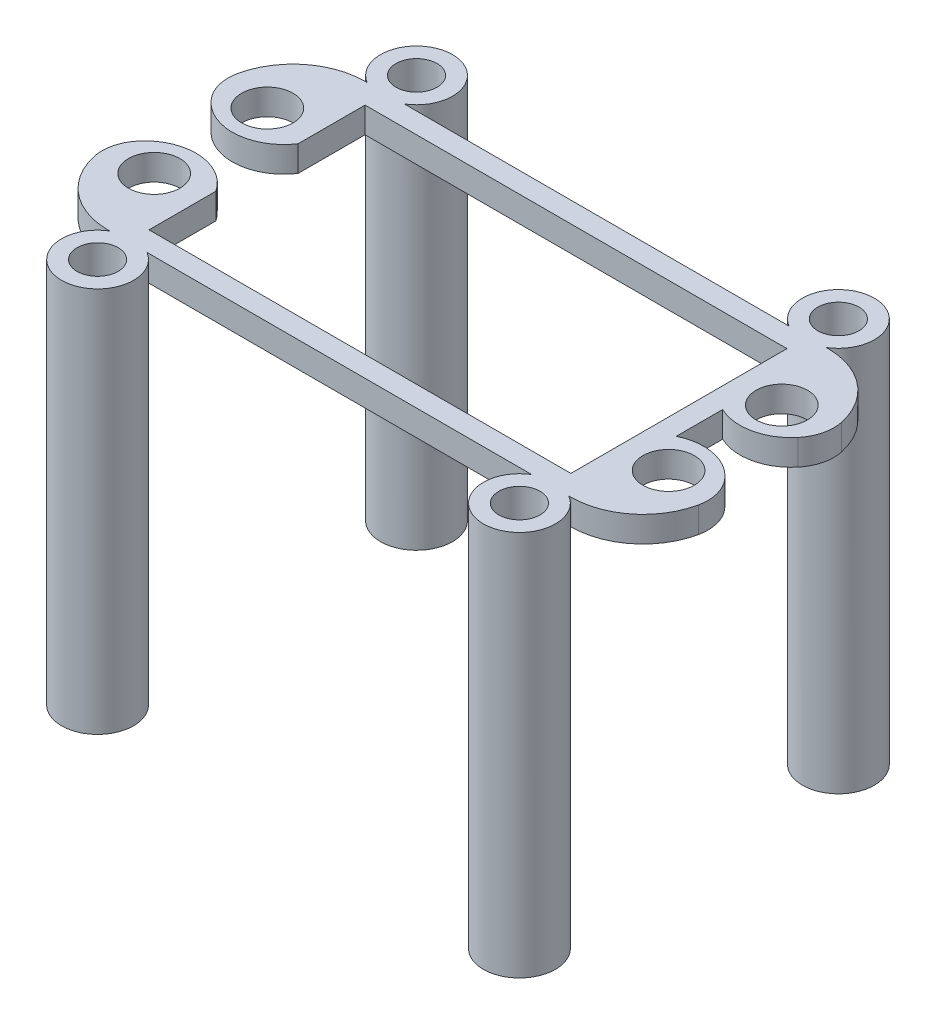
SolidWorks part; units mm, degrees
ref_plane "Front Plane" through (0, 0, 0) normal (0, 0, 1) x (1, 0, 0)
ref_plane "Top Plane" through (0, 0, 0) normal (0, 1, 0) x (1, 0, 0)
ref_plane "Right Plane" through (0, 0, 0) normal (1, 0, 0) x (0, 0, -1)
sketch "Sketch1" plane through (0, 0, 0) normal (0, 1, 0) x (1, 0, 0)
  line L0 (-20, 0) -> (-22, 0) construction
  line L1 (20.5, 10.5) -> (-20.5, 10.5)
  line L2 (20.5, 10.5) -> (20.5, -10.5)
  line L3 (20.5, -10.5) -> (-20.5, -10.5)
  line L4 (-20.5, 10.5) -> (-20.5, 4)
  line L5 (20.5, 10.5) -> (-20.5, -10.5) construction
  line L6 (20.5, -10.5) -> (-20.5, 10.5) construction
  line L7 (22.5, 12.5) -> (-22.5, 12.5)
  line L8 (22.5, 2.2557) -> (22.5, -2.2557)
  line L9 (22.5, -12.5) -> (-22.5, -12.5)
  line L11 (22.5, 12.5) -> (-22.5, -12.5) construction
  line L12 (22.5, -12.5) -> (-22.5, 12.5) construction
  line L16 (-20.5, -4) -> (-20.5, -10.5)
  line L17 (0, 0) -> (-37.8746, 0) construction
  line L18 (0, 0) -> (0, 8.5057) construction
  circle A0 centre (-25, 5.5) radius 2.5
  circle A1 centre (-25, -5.5) radius 2.5
  arc A4 (-22.5, 12.5) -> (-29.3504, 6.9605) centre (-22.5, 5.4945) ccw
  arc A5 (-20.5, 4) -> (-28.5206, 3.5732) centre (-24.6686, 6.761) cw
  arc A6 (-20.5, -4) -> (-28.5206, -3.5732) centre (-24.6686, -6.761) ccw
  arc A7 (-22.5, -12.5) -> (-29.3504, -6.9605) centre (-22.5, -5.4945) cw
  arc A8 (22.5, -12.5) -> (29.3504, -6.9605) centre (22.5, -5.4945) ccw
  circle A9 centre (25, -5.5) radius 2.5
  arc A10 (22.5, -2.2557) -> (28.5206, -3.5732) centre (24.6686, -6.761) cw
  circle A11 centre (25, 5.5) radius 2.5
  arc A12 (22.5, 2.2557) -> (28.5206, 3.5732) centre (24.6686, 6.761) ccw
  arc A13 (22.5, 12.5) -> (29.3504, 6.9605) centre (22.5, 5.4945) cw
  arc A14 (29.3504, -6.9605) -> (28.5206, -3.5732) centre (25.439, -6.1234) ccw
  arc A15 (28.5206, 3.5732) -> (29.3504, 6.9605) centre (25.439, 6.1234) ccw
  arc A16 (-28.5206, -3.5732) -> (-29.3504, -6.9605) centre (-25.439, -6.1234) ccw
  arc A17 (-29.3504, 6.9605) -> (-28.5206, 3.5732) centre (-25.439, 6.1234) ccw
  point P0 (0, 0)
  point P6 (0, 0)
  point P13 (-21, 0)
  point P36 (29.5055, -5.4945)
  point P46 (29.5055, 5.4945)
  point P49 (-29.5055, -5.4945)
  point P52 (-29.5055, 5.4945)
  dimension "D6" = 5
  dimension "D8" = 4.5
  dimension "D9" = 11
  dimension "D10" = 5
  dimension "D5" = 4
  dimension "D2" = 2
  dimension "D3" = 41
  dimension "D4" = 21
extrude "Boss-Extrude1" add sketch "Sketch1" along normal blind 2.5
sketch "Sketch4" plane through (0, 0, 0) normal (0, 1, 0) x (1, 0, 0)
  line L0 (-20.5, -10.5) -> (-20.5, -12.5) construction
  line L1 (-20.5, 10.5) -> (-20.5, 12.5) construction
  line L2 (22.5, 12.5) -> (-22.5, 12.5) construction
  line L3 (-20.5, 12.5) -> (-20.5, 15.5) construction
  line L4 (0, 0) -> (-12.5316, 0) construction
  line L5 (-22.5, -12.5) -> (22.5, -12.5) construction
  line L6 (-20.5, -12.5) -> (-20.5, -15.5) construction
  circle A0 centre (-20.5, 15.5) radius 2
  circle A1 centre (-20.5, 15.5) radius 3.5
  circle A2 centre (20.5, 15.5) radius 2
  circle A3 centre (20.5, 15.5) radius 3.5
  circle A4 centre (-20.5, -15.5) radius 2
  circle A5 centre (-20.5, -15.5) radius 3.5
  circle A6 centre (20.5, -15.5) radius 2
  circle A7 centre (20.5, -15.5) radius 3.5
  dimension "D1" = 1.5
  dimension "D2" = 4
  dimension "D3" = 1.5
  dimension "D4" = 4
  dimension "D8" = 4
  dimension "D9" = 1.5
  dimension "D10" = 1.5
  dimension "D11" = 4
  dimension "D5" = 41
  dimension "D6" = 3
  dimension "D7" = 41
  dimension "D12" = 3
extrude "Boss-Extrude2" add sketch "Sketch4" along normal up to surface (2.5 mm away) and the other way blind 35 up to face at (0.2335, 2.5, 0)
